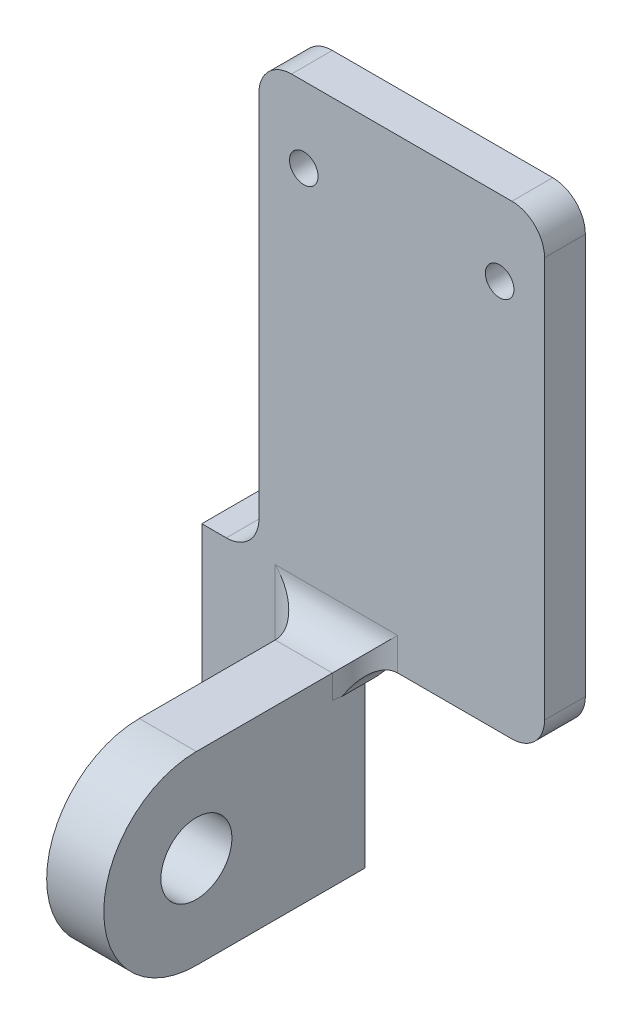
SolidWorks part; units mm, degrees
ref_plane "Front Plane" through (0, 0, 0) normal (0, 0, 1) x (1, 0, 0)
ref_plane "Top Plane" through (0, 0, 0) normal (0, 1, 0) x (1, 0, 0)
ref_plane "Right Plane" through (0, 0, 0) normal (1, 0, 0) x (0, 0, -1)
sketch "Sketch1" plane through (0, 0, 0) normal (0, 0, 1) x (1, 0, 0)
  line L0 (0, 0) -> (0, 17.9673) construction
  line L1 (-17.5, -30) -> (17.5, -30)
  line L2 (-17.5, -30) -> (-17.5, 30)
  line L3 (-17.5, 30) -> (17.5, 30)
  line L4 (17.5, -30) -> (17.5, 30)
  line L5 (-17.5, -30) -> (17.5, 30) construction
  line L6 (-17.5, 30) -> (17.5, -30) construction
  line L7 (-17.5, -0.5) -> (17.5, -0.5) construction
  circle A0 centre (-12, 20.75) radius 1.75
  circle A1 centre (12, 20.75) radius 1.75
  point P0 (0, 0)
  dimension "D3" = 3.5
  dimension "D1" = 60
  dimension "D2" = 35
  dimension "D4" = 12
  dimension "D5" = 9.25
  dimension "D6" = 21.25
extrude "Boss-Extrude1" add sketch "Sketch1" along normal blind 5
sketch "Sketch5" plane through (-17.5, 0, 0) normal (-1, 0, 0) x (0, 0, 1)
  line L1 (5, -30) -> (5, -48.6535) construction
  line L3 (-13.9089, -41.9254) -> (5, -41.9254)
  line L10 (-13.9089, -23.2254) -> (5, -23.2254)
  line L11 (5, 30) -> (5, -30) construction
  line L12 (5, -23.2254) -> (5, -41.9254)
  circle A0 centre (-13.9089, -32.5754) radius 4.35
  arc A2 (-13.9089, -23.2254) -> (-13.9089, -41.9254) centre (-13.9089, -32.5754) ccw
  dimension "D1" = 8.7
  dimension "D2" = 5
ref_plane "Plane2" through (-4.5, 0, 0) normal (-1, 0, 0) x (0, 0, 1)
extrude "Boss-Extrude5" add sketch "Sketch5" along normal blind 7
sketch "Sketch9" plane through (-4.5, 0, 0) normal (-1, 0, 0) x (0, 0, 1)
  line L0 (-13.9089, -32.5754) -> (25.662, -38.4187) construction
  line L1 (-13.9089, -32.5754) -> (-13.9089, 15.7357) construction
  line L3 (25.662, -27.0687) -> (0, -27.0687)
  line L4 (0, -30) -> (0, 30) construction
  line L5 (0, -41.3889) -> (0, 30) construction
  line L6 (25.662, -49.7687) -> (0, -49.7687)
  line L7 (0, -49.7687) -> (0, -27.0687)
  circle A0 centre (-13.9089, -32.5754) radius 4.35 construction
  circle A1 centre (-13.9089, -32.5754) radius 4.35 construction
  circle A2 centre (25.662, -38.4187) radius 4.35
  arc A3 (25.662, -49.7687) -> (25.662, -27.0687) centre (25.662, -38.4187) ccw
  dimension "D1" = 8.7
  dimension "D2" = 7
  dimension "D3" = 98.4
  dimension "D4" = 40
extrude "Boss-Extrude7" add sketch "Sketch9" along normal blind 7
sketch "Sketch10" plane through (-4.5, 0, 0) normal (1, 0, 0) x (0, 0, -1)
  line L0 (0, -30) -> (0, -49.7687)
  line L1 (0, -30) -> (-5, -30)
  line L2 (-5, -30) -> (-5, -49.7687)
  line L3 (0, -49.7687) -> (-25.662, -49.7687) construction
  line L4 (-5, -49.7687) -> (0, -49.7687)
extrude "Cut-Extrude2" cut sketch "Sketch10" against normal blind 7
sketch "Sketch11" plane through (0, 0, 5) normal (0, 0, 1) x (1, 0, 0)
  line L0 (-4.5, -27.0687) -> (17.5, -27.0687)
  line L1 (17.5, -30) -> (17.5, 30) construction
  line L2 (-4.5, -27.0687) -> (-4.5, -30)
  line L3 (-4.5, -30) -> (17.5, -30)
  line L4 (17.5, -30) -> (17.5, -27.0687)
extrude "Cut-Extrude3" cut sketch "Sketch11" against normal blind 7
fillet "Fillet1" radius 10 1 edges at (-17.5, -30, 2.5)
fillet "Fillet2" radius 4 1 edges at (-4.5, -27.0687, 2.5)
fillet "Fillet3" radius 4 1 edges at (17.5, -27.0687, 2.5)
fillet "Fillet4" radius 4 1 edges at (-17.5, -23.2254, 2.5)
fillet "Fillet5" radius 4 1 edges at (-17.5, 30, 2.5)
fillet "Fillet6" radius 4 1 edges at (17.5, 30, 2.5)
fillet "Fillet8" radius 4 1 edges at (-19.5, -23.2254, 0)
fillet "Fillet9" radius 4 1 edges at (-8, -27.0687, 5)
fillet "Fillet10" radius 4 1 edges at (-4.5, -26.5343, 5)
fillet "Fillet11" radius 4 1 edges at (-11.5, -26.9518, 5)
fillet "Fillet12" radius 4 2 edges at (-14.5711, -32.9289, 0) (-5.9273, -30, 0)
ref_plane "Plane3" through (0, -32.5754, 0) normal (0, 1, 0) x (1, 0, 0)
